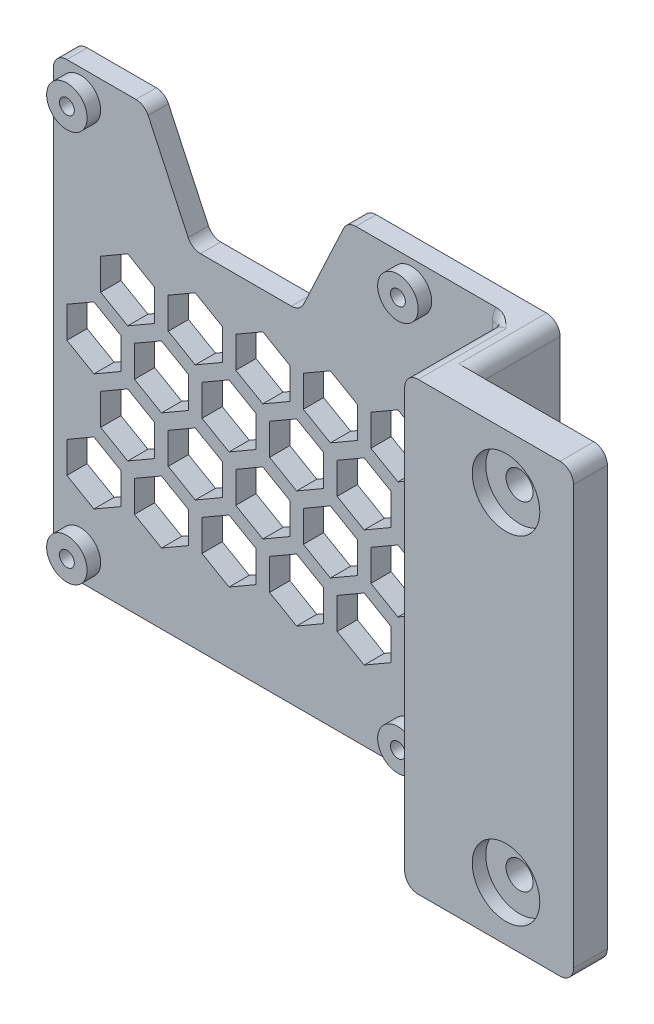
SolidWorks part; units mm, degrees
ref_plane "Plan de face" through (0, 0, 0) normal (0, 0, 1) x (1, 0, 0)
ref_plane "Plan de dessus" through (0, 0, 0) normal (0, 1, 0) x (1, 0, 0)
ref_plane "Plan de droite" through (0, 0, 0) normal (1, 0, 0) x (0, 0, -1)
sketch "Esquisse1" plane through (0, 0, 0) normal (0, 0, 1) x (1, 0, 0)
  line L1 (-60.2259, 25.9653) -> (-11.2259, 25.9653) construction
  line L2 (-60.2259, 25.9653) -> (-60.2259, -32.0347) construction
  line L3 (-60.2259, -32.0347) -> (-11.2259, -32.0347) construction
  line L4 (-11.2259, 25.9653) -> (-11.2259, -32.0347) construction
  line L5 (-64.2259, 29.9653) -> (-7.2259, 29.9653)
  line L6 (-64.2259, 29.9653) -> (-64.2259, -36.0347)
  line L7 (-64.2259, -36.0347) -> (-7.2259, -36.0347)
  line L8 (-7.2259, 29.9653) -> (-7.2259, -36.0347)
  circle A0 centre (-60.2259, 25.9653) radius 3
  circle A1 centre (-11.2259, 25.9653) radius 3
  circle A2 centre (-11.2259, -32.0347) radius 3
  circle A3 centre (-60.2259, -32.0347) radius 3
  circle A4 centre (-60.2259, 25.9653) radius 1.1
  circle A5 centre (-11.2259, 25.9653) radius 1.1
  circle A6 centre (-60.2259, -32.0347) radius 1.1
  circle A7 centre (-11.2259, -32.0347) radius 1.1
  dimension "D7" = 6
  dimension "D8" = 2.2
  dimension "D1" = 58
  dimension "D2" = 49
  dimension "D3" = 4
  dimension "D4" = 4
  dimension "D5" = 4
  dimension "D6" = 4
extrude "Boss.-Extru.1" add sketch "Esquisse1" along normal blind 3 contours L8 L5 L6 L7 A3 A2 A1 A0 region at (-35.7259, -3.0347, 0)
extrude "Boss.-Extru.2" add sketch "Esquisse1<3>" along normal blind 5 contours A0 A4 | A3 A6 | A2 A7 | A1 A5 region at (-63.141, 25.9653, 0) region at (-14.141, 25.9653, 0) region at (-14.141, -32.0347, 0) region at (-63.141, -32.0347, 0)
sketch "Esquisse1<3>" plane through (0, 0, 0) normal (0, 0, 1) x (1, 0, 0) same geometry as "Esquisse1"
sketch "Esquisse4" plane through (0, -36.0347, 0) normal (0, -1, 0) x (1, 0, 0)
  line L0 (-7.2259, 3) -> (2.7741, 3)
  line L1 (2.7741, 3) -> (2.7741, 18)
  line L2 (2.7741, 18) -> (27.7741, 18)
  line L3 (27.7741, 18) -> (27.7741, 13)
  line L4 (27.7741, 13) -> (7.7741, 13)
  line L5 (7.7741, 13) -> (7.7741, 0)
  line L6 (7.7741, 0) -> (-7.2259, 0)
  line L7 (-7.2259, 0) -> (-7.2259, 3)
  dimension "D1" = 13
  dimension "D2" = 5
  dimension "D3" = 20
  dimension "D4" = 5
  dimension "D5" = 10
extrude "Boss.-Extru.3" add sketch "Esquisse4" against normal up to surface (66 mm away) up to face at (-35.7259, 29.9653, 1.5)
sketch "Esquisse5" plane through (0, 0, 18) normal (0, 0, 1) x (1, 0, 0)
  line L0 (17.7741, -36.0347) -> (17.7741, 29.9653) construction
  line L1 (27.7741, -36.0347) -> (2.7741, -36.0347) construction
  line L2 (27.7741, 29.9653) -> (2.7741, 29.9653) construction
  line L3 (27.7741, 29.9653) -> (27.7741, -36.0347) construction
  line L4 (17.7741, 21.9653) -> (17.7741, -28.0347) construction
  circle A0 centre (17.7741, -28.0347) radius 2
  circle A1 centre (17.7741, 21.9653) radius 2
  circle A2 centre (17.7741, -28.0347) radius 5
  circle A3 centre (17.7741, 21.9653) radius 5
  point P13 (17.7741, -3.0347)
  point P14 (17.7741, -3.0347)
  dimension "D3" = 4
  dimension "D4" = 10
  dimension "D1" = 10
  dimension "D2" = 50
extrude "Enlèv. mat.-Extru.1" cut sketch "Esquisse5" against normal through all both and the other way through all contours A0 | A1
extrude "Enlèv. mat.-Extru.2" cut sketch "Esquisse5<3>" against normal blind 2
sketch "Esquisse5<3>" plane through (0, 0, 18) normal (0, 0, 1) x (1, 0, 0) same geometry as "Esquisse5"
sketch "Esquisse6" plane through (0, 0, 3) normal (0, 0, 1) x (1, 0, 0)
  line L0 (-50.7259, 29.9653) -> (-43.7313, 14.9653)
  line L1 (-64.2259, 29.9653) -> (2.7741, 29.9653) construction
  line L2 (-43.7313, 14.9653) -> (-27.7205, 14.9653)
  line L3 (-27.7205, 14.9653) -> (-20.7259, 29.9653)
  line L4 (-20.7259, 29.9653) -> (-50.7259, 29.9653)
  line L5 (-60.2259, 25.9653) -> (-11.2259, 25.9653) construction
  point P6 (-35.7259, 25.9653)
  point P11 (-35.7259, 14.9653)
  dimension "D1" = 65
  dimension "D2" = 65
  dimension "D3" = 15
  dimension "D4" = 30
extrude "Enlèv. mat.-Extru.3" cut sketch "Esquisse6" against normal through all both and the other way through all
sketch "Esquisse7" plane through (0, 0, 3) normal (0, 0, 1) x (1, 0, 0)
  line L0 (-64.2259, 29.9653) -> (-64.2259, -36.0347) construction
  line L1 (-54.2259, -18.7253) -> (-58.2259, -16.4159)
  line L2 (-58.2259, -16.4159) -> (-62.2259, -18.7253)
  line L3 (-62.2259, -18.7253) -> (-62.2259, -23.3441)
  line L4 (-62.2259, -23.3441) -> (-58.2259, -25.6535)
  line L5 (-58.2259, -25.6535) -> (-54.2259, -23.3441)
  line L6 (-54.2259, -23.3441) -> (-54.2259, -18.7253)
  line L7 (-64.2259, -36.0347) -> (2.7741, -36.0347) construction
  line L8 (-56.2259, -17.5706) -> (-53.5999, -13.0223) construction
  circle A0 centre (-58.2259, -21.0347) radius 4 construction
  dimension "D1" = 8
  dimension "D2" = 6
  dimension "D3" = 15
extrude "Enlèv. mat.-Extru.4" cut sketch "Esquisse7" against normal through all both and the other way through all
pattern_linear "Répétition linéaire1" count 6 spacing 10 along (1, 0, 0) count 2 spacing 10 along (0.5, 0.866, 0) of "Enlèv. mat.-Extru.4"
pattern_linear "Répétition linéaire2" count 2 spacing 17.32 along (0, 1, 0) of "Répétition linéaire1"
fillet "Congé1" radius 2 12 edges at (27.7741, -36.0347, 15.5) (27.7741, 29.9653, 15.5) (2.7741, 29.9653, 10.5) (2.7741, -36.0347, 10.5) (7.7741, -36.0347, 6.5) (7.7741, 29.9653, 6.5) (-20.7259, 29.9653, 1.5) (-27.7205, 14.9653, 1.5) (-43.7313, 14.9653, 1.5) (-50.7259, 29.9653, 1.5) (-64.2259, 29.9653, 1.5) (-64.2259, -36.0347, 1.5)
fillet "Congé3" radius 2 3 edges at (3.3599, 29.3795, 3) (3.3599, -35.4489, 3) (2.7741, -3.0347, 3)
